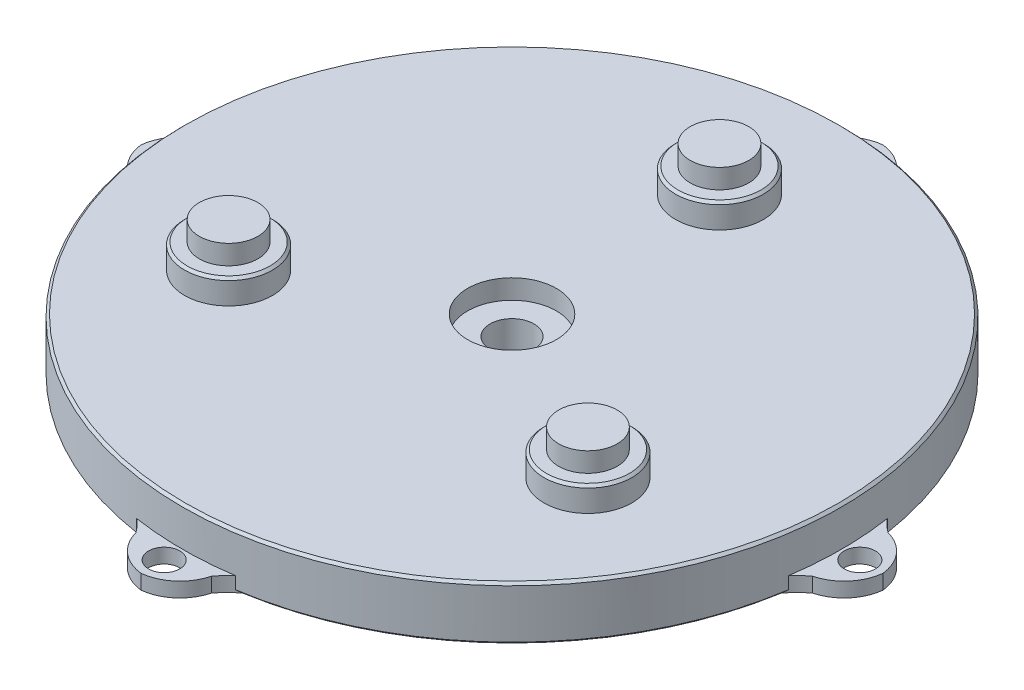
SolidWorks part; units mm, degrees
ref_plane "Front Plane" through (0, 0, 0) normal (0, 0, 1) x (1, 0, 0)
ref_plane "Top Plane" through (0, 0, 0) normal (0, 1, 0) x (1, 0, 0)
ref_plane "Right Plane" through (0, 0, 0) normal (1, 0, 0) x (0, 0, -1)
sketch "Sketch2" plane through (0, 0, 0) normal (0, 1, 0) x (1, 0, 0)
  circle A0 centre (0, 0) radius 65
  dimension "D1" = 130
extrude "Boss-Extrude1" add sketch "Sketch2" along normal blind 11
sketch "Sketch3" plane through (0, 11, 0) normal (0, 1, 0) x (1, 0, 0)
  circle A1 centre (0, 0) radius 9.1
  dimension "D2" = 18.2
extrude "Cut-Extrude2" cut sketch "Sketch3" against normal blind 4
sketch "Sketch4" plane through (0, 7, 0) normal (0, 1, 0) x (1, 0, 0)
  circle A0 centre (0, 0) radius 4.5
  dimension "D1" = 9
extrude "Cut-Extrude4" cut sketch "Sketch4" against normal blind 20
sketch "Sketch5" plane through (0, 0, 0) normal (0, -1, 0) x (1, 0, 0)
  circle A0 centre (0, 0) radius 67.5
  circle A1 centre (0, 0) radius 65
  dimension "D1" = 135
  dimension "D2" = 130
extrude "Boss-Extrude3" add sketch "Sketch5" against normal blind 11
chamfer "Chamfer1" distance 0.5 angle 45 1 edges at (0, 11, -67.5)
chamfer "Chamfer2" distance 0.5 angle 45 1 edges at (0, 0, -67.5)
sketch "Sketch6" plane through (0, 0, 0) normal (0, -1, 0) x (1, 0, 0)
  line L0 (0, 0) -> (0, 77.7457) construction
  line L1 (0, 67) -> (0, 74)
  circle A2 centre (0, 0) radius 67
  circle A4 centre (0, 0) radius 75
  arc A5 (-5.994, 66.7313) -> (0, 74) centre (-0.1299, 68.0014) cw
  arc A6 (5.994, 66.7313) -> (0, 74) centre (0.1299, 68.0014) ccw
  arc A7 (66.7313, -5.994) -> (74, 0) centre (68.0014, -0.1299) ccw
  arc A8 (66.7313, 5.994) -> (74, 0) centre (68.0014, 0.1299) cw
  arc A9 (-5.994, -66.7313) -> (0, -74) centre (-0.1299, -68.0014) ccw
  arc A10 (5.994, -66.7313) -> (0, -74) centre (0.1299, -68.0014) cw
  arc A11 (-66.7313, 5.994) -> (-74, 0) centre (-68.0014, 0.1299) ccw
  arc A12 (-66.7313, -5.994) -> (-74, 0) centre (-68.0014, -0.1299) cw
  arc A13 (-7.9831, 66.5227) -> (-6.0375, 69.0503) centre (-11.5939, 71.3145) ccw
  arc A14 (7.9831, 66.5227) -> (6.0375, 69.0503) centre (11.5939, 71.3145) cw
  arc A15 (66.5227, 7.9831) -> (69.0503, 6.0375) centre (71.3145, 11.5939) ccw
  arc A16 (66.5227, -7.9831) -> (69.0503, -6.0375) centre (71.3145, -11.5939) cw
  arc A17 (7.9831, -66.5227) -> (6.0375, -69.0503) centre (11.5939, -71.3145) ccw
  arc A18 (-7.9831, -66.5227) -> (-6.0375, -69.0503) centre (-11.5939, -71.3145) cw
  arc A19 (-66.5227, -7.9831) -> (-69.0503, -6.0375) centre (-71.3145, -11.5939) ccw
  arc A20 (-66.5227, 7.9831) -> (-69.0503, 6.0375) centre (-71.3145, 11.5939) cw
  point P29 (0, 0)
  point P30 (0, 0)
  point P55 (0, 0)
  circle M6 centre (0, 0) radius 67
  dimension "D1" = 150
  dimension "D2" = 134
  dimension "D4" = 6
  dimension "D8" = 6
  dimension "D3" = 7
  dimension "D5" = 6
  dimension "D7" = 2
  dimension "D6" = 4
  dimension "D9" = 4
extrude "Boss-Extrude8" add sketch "Sketch6" against normal blind 3 contours A5 L1 M6 | A6 L1 M6 | A14 A6 M6 | A13 A2 A5 | A8 A7 M6 | A15 A2 A8 | A16 A7 M6 | A10 A9 M6 | A18 A9 M6 | A17 A2 A10 | A12 A11 M6 | A2 A20 A11 | A19 A2 A12 region at (-2.7115, 0, 69.9813) region at (2.7115, 0, 69.9813) region at (6.6591, 0, 67.309) region at (-6.6591, 0, 67.309) region at (67.309, 0, 6.6591) region at (-67.309, 0, 6.6591) region at (69.9813, 0, 0) region at (-69.9813, 0, 0) region at (-67.309, 0, -6.6591) region at (67.309, 0, -6.6591) region at (-6.6591, 0, -67.309) region at (6.6591, 0, -67.309) region at (0, 0, -69.9813)
sketch "Sketch7" plane through (0, 0, 0) normal (0, -1, 0) x (1, 0, 0)
  line L0 (0, 0) -> (0, 118.4865) construction
  line L1 (0, 67) -> (0, 76)
  circle A0 centre (0, 0) radius 82.5
  circle A1 centre (0, 0) radius 67
  arc A2 (-8, 66.5207) -> (0, 76) centre (0.9842, 67.054) cw
  arc A3 (-10.9698, 66.0959) -> (-7.7257, 69.3206) centre (-19.0851, 77.5039) ccw
  arc A4 (8, 66.5207) -> (0, 76) centre (-0.9842, 67.054) ccw
  arc A5 (10.9698, 66.0959) -> (7.7257, 69.3206) centre (19.0851, 77.5039) cw
  arc A6 (66.0959, 10.9698) -> (69.3206, 7.7257) centre (77.5039, 19.0851) ccw
  arc A7 (66.5207, 8) -> (76, 0) centre (67.054, -0.9842) cw
  arc A8 (66.5207, -8) -> (76, 0) centre (67.054, 0.9842) ccw
  arc A9 (66.0959, -10.9698) -> (69.3206, -7.7257) centre (77.5039, -19.0851) cw
  arc A10 (10.9698, -66.0959) -> (7.7257, -69.3206) centre (19.0851, -77.5039) ccw
  arc A11 (8, -66.5207) -> (0, -76) centre (-0.9842, -67.054) cw
  arc A12 (-8, -66.5207) -> (0, -76) centre (0.9842, -67.054) ccw
  arc A13 (-10.9698, -66.0959) -> (-7.7257, -69.3206) centre (-19.0851, -77.5039) cw
  arc A14 (-66.0959, -10.9698) -> (-69.3206, -7.7257) centre (-77.5039, -19.0851) ccw
  arc A15 (-66.5207, -8) -> (-76, 0) centre (-67.054, 0.9842) cw
  arc A16 (-66.5207, 8) -> (-76, 0) centre (-67.054, -0.9842) ccw
  arc A17 (-66.0959, 10.9698) -> (-69.3206, 7.7257) centre (-77.5039, 19.0851) cw
  point P53 (0, 0)
  arc M21 (-7.9831, 66.5227) -> (-66.5227, 7.9831) centre (0, 0) ccw
  arc M22 (-66.5227, 7.9831) -> (-69.0503, 6.0375) centre (-71.3145, 11.5939) cw
  arc M23 (-69.0503, 6.0375) -> (-74, 0) centre (-68.0014, 0.1299) ccw
  arc M24 (-74, 0) -> (-69.0503, -6.0375) centre (-68.0014, -0.1299) ccw
  arc M25 (-69.0503, -6.0375) -> (-66.5227, -7.9831) centre (-71.3145, -11.5939) cw
  arc M26 (-66.5227, -7.9831) -> (-7.9831, -66.5227) centre (0, 0) ccw
  arc M27 (-7.9831, -66.5227) -> (-6.0375, -69.0503) centre (-11.5939, -71.3145) cw
  arc M28 (-6.0375, -69.0503) -> (0, -74) centre (-0.1299, -68.0014) ccw
  arc M29 (0, -74) -> (6.0375, -69.0503) centre (0.1299, -68.0014) ccw
  arc M30 (6.0375, -69.0503) -> (7.9831, -66.5227) centre (11.5939, -71.3145) cw
  arc M31 (7.9831, -66.5227) -> (66.5227, -7.9831) centre (0, 0) ccw
  arc M32 (66.5227, -7.9831) -> (69.0503, -6.0375) centre (71.3145, -11.5939) cw
  arc M33 (69.0503, -6.0375) -> (74, 0) centre (68.0014, -0.1299) ccw
  arc M34 (74, 0) -> (69.0503, 6.0375) centre (68.0014, 0.1299) ccw
  arc M35 (69.0503, 6.0375) -> (66.5227, 7.9831) centre (71.3145, 11.5939) cw
  arc M36 (66.5227, 7.9831) -> (7.9831, 66.5227) centre (0, 0) ccw
  arc M37 (7.9831, 66.5227) -> (6.0375, 69.0503) centre (11.5939, 71.3145) cw
  arc M38 (6.0375, 69.0503) -> (0, 74) centre (0.1299, 68.0014) ccw
  arc M39 (0, 74) -> (-6.0375, 69.0503) centre (-0.1299, 68.0014) ccw
  arc M40 (-6.0375, 69.0503) -> (-7.9831, 66.5227) centre (-11.5939, 71.3145) cw
  dimension "D1" = 165
  dimension "D2" = 134
  dimension "D5" = 9
  dimension "D7" = 14
  dimension "D3" = 9
  dimension "D4" = 8
  dimension "D6" = 3
  dimension "D8" = 4
extrude "Boss-Extrude9" add sketch "Sketch7" against normal blind 3 contours A2 L1 M21 M40 M39 | A1 A4 L1 M38 M37 | A1 A5 A4 | A3 A1 A2 | A1 A16 A15 M26 M25 M24 M23 M22 | A1 A17 A16 | A1 A15 A14 | A1 A13 A12 | A1 A12 A11 M31 M30 M29 M28 M27 | A1 A11 A10 | A1 A9 A8 | A1 A8 A7 M36 M35 M34 M33 M32 | A1 A7 A6 region at (-4.5122, 0, 72.1843) region at (4.5122, 0, 72.1843) region at (8.8859, 0, 67.2239) region at (-8.8859, 0, 67.2239) region at (67.2239, 0, 8.8859) region at (-67.2239, 0, 8.8859) region at (67.9133, 0, 7.7876) region at (-66.5402, 0, 7.9938) region at (67.2239, 0, -8.8859) region at (-67.2239, 0, -8.8859) region at (8.8859, 0, -67.2239) region at (-8.8859, 0, -67.2239) region at (7.7876, 0, -67.9133)
sketch "Sketch8" plane through (0, 0, 0) normal (0, -1, 0) x (1, 0, 0)
  circle A1 centre (0, 71.25) radius 3.2
  circle A2 centre (71.25, 0) radius 3.2
  circle A3 centre (0, -71.25) radius 3.2
  circle A4 centre (-71.25, 0) radius 3.2
  point P14 (0, 0)
  dimension "D2" = 6.4
  dimension "D3" = 4
extrude "Cut-Extrude5" cut sketch "Sketch8" against normal blind 4
sketch "Sketch9" plane through (0, 11, 0) normal (0, 1, 0) x (1, 0, 0)
  line L0 (0, 0) -> (0, 88.7955) construction
  circle A0 centre (0, 0) radius 17.5
  circle A1 centre (0, 0) radius 42.5
  circle A4 centre (0, 42.5) radius 9
  circle A5 centre (0, 0) radius 9.1
  circle A6 centre (36.8061, -21.25) radius 9
  circle A7 centre (-36.8061, -21.25) radius 9
  point P15 (0, 0)
  dimension "D1" = 35
  dimension "D2" = 85
  dimension "D3" = 3
  dimension "D5" = 18
extrude "Boss-Extrude10" add sketch "Sketch9" along normal blind 5 contours L0 A1 A4 | A1 L0 A4 | A4 L0 A1 | L0 A4 A1 | A1 A7 | A1 A7 | A1 A6 | A1 A6 region at (-3.682, 11, -38.5138) region at (3.682, 11, -38.5138) region at (-3.9455, 11, -46.143) region at (3.9455, 11, -46.143) region at (-33.3539, 11, 19.2569) region at (-39.961, 11, 23.0715) region at (39.961, 11, 23.0715) region at (33.3539, 11, 19.2569)
sketch "Sketch10" plane through (0, 16, 0) normal (0, 1, 0) x (1, 0, 0)
  circle A1 centre (0, 42.5) radius 6
  circle A2 centre (36.8061, -21.25) radius 6
  circle A3 centre (-36.8061, -21.25) radius 6
  point P9 (0, 0)
  dimension "D1" = 3
  dimension "D2" = 12
extrude "Boss-Extrude11" add sketch "Sketch10" along normal blind 4
chamfer "Chamfer4" distance 0.5 angle 45 3 edges at (36.8061, 16, 30.25) (-36.8061, 16, 30.25) (0, 16, -33.5)
sketch "Sketch11" plane through (0, 0, 0) normal (0, -1, 0) x (1, 0, 0)
  line L1 (0, 28.5) -> (-28.5, 28.5)
  line L2 (0, 28.5) -> (28.5, 28.5)
  line L3 (-28.5, 28.5) -> (-28.5, -28.5)
  line L4 (-28.5, -28.5) -> (28.5, -28.5)
  line L5 (28.5, -28.5) -> (28.5, 28.5)
  circle A0 centre (-23.5, -23.5) radius 2.5
  circle A1 centre (-23.5, 23.5) radius 2.5
  circle A2 centre (23.5, 23.5) radius 2.5
  circle A3 centre (23.5, -23.5) radius 2.5
  dimension "D8" = 5
  dimension "D9" = 5
  dimension "D10" = 5
  dimension "D11" = 5
  dimension "D2" = 57
  dimension "D3" = 28.5
  dimension "D4" = 57
  dimension "D6" = 47
  dimension "D7" = 47
